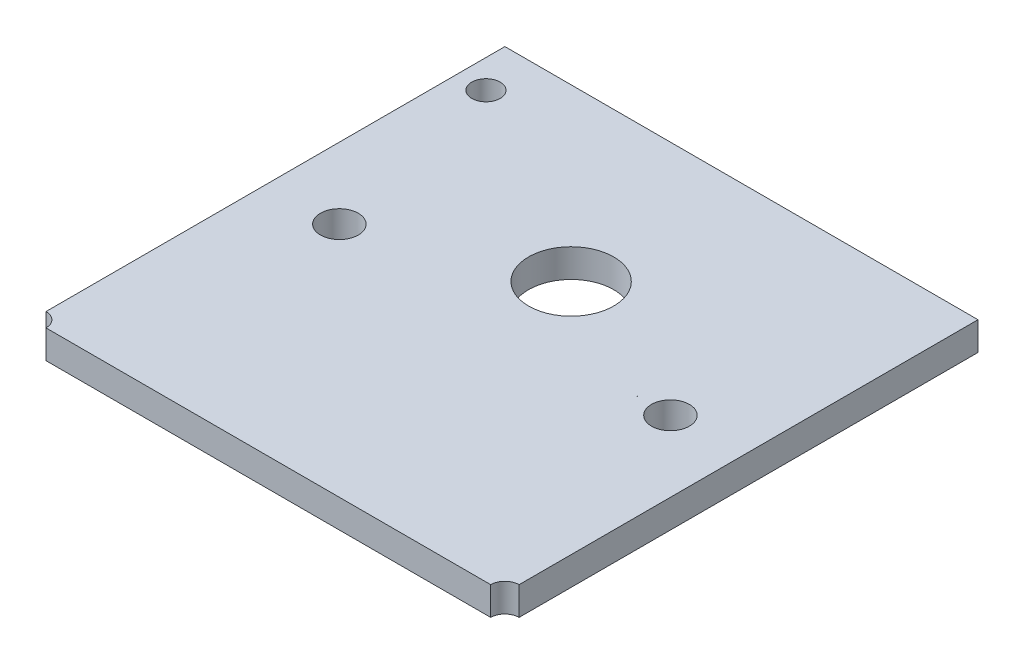
SolidWorks part; units mm, degrees
ref_plane "Front Plane" through (0, 0, 0) normal (0, 0, 1) x (1, 0, 0)
ref_plane "Top Plane" through (0, 0, 0) normal (0, 1, 0) x (1, 0, 0)
ref_plane "Right Plane" through (0, 0, 0) normal (1, 0, 0) x (0, 0, -1)
sketch "Sketch1" plane through (0, 0, 0) normal (0, 1, 0) x (1, 0, 0)
  line L0 (-25, 20) -> (25, 20) construction
  line L1 (-25, -25) -> (25, -25)
  line L2 (-25, -25) -> (-25, 25)
  line L3 (-25, 25) -> (25, 25)
  line L4 (25, -25) -> (25, 25)
  line L5 (-25, -25) -> (25, 25) construction
  line L6 (-25, 25) -> (25, -25) construction
  line L7 (-22, 25) -> (-22, -25) construction
  line L8 (-17.4954, -3.5) -> (-13.5554, -3.5)
  line L9 (-17.4954, 3.5) -> (-13.5554, 3.5)
  line L10 (0, 0) -> (0, -3.5) construction
  line L11 (17.4954, -3.5) -> (13.5554, -3.5)
  line L12 (17.4954, 3.5) -> (13.5554, 3.5)
  circle A0 centre (-22, 20) radius 1.5
  circle A1 centre (28, 20) radius 1.5
  circle A2 centre (25, -25) radius 1.5
  circle A3 centre (-25, -25) radius 1.5
  circle A8 centre (0, 0) radius 14
  circle A9 centre (0, 7) radius 4.5
  arc A10 (-17.4954, 3.5) -> (-17.4954, -3.5) centre (-17.4954, 0) ccw
  circle A11 centre (-17.4954, 0) radius 2
  circle A12 centre (17.4954, 0) radius 2
  arc A13 (17.4954, 3.5) -> (17.4954, -3.5) centre (17.4954, 0) cw
  arc A14 (-13.9991, -0.1597) -> (-13.9991, 0.1597) centre (-17.4954, 0) ccw
  arc A15 (13.9991, -0.1597) -> (13.9991, 0.1597) centre (17.4954, 0) cw
  point P0 (0, 0)
  dimension "D5" = 2
  dimension "D6" = 28
  dimension "D7" = 7
  dimension "D8" = 3.94
  dimension "D10" = 7
  dimension "D11" = 3
  dimension "D12" = 3
  dimension "D13" = 3
  dimension "D14" = 50
  dimension "D1" = 50
  dimension "D2" = 50
  dimension "D3" = 3
  dimension "D4" = 5
  dimension "D9" = 3.94
extrude "Boss-Extrude1" add sketch "Sketch1" along normal blind 3 contours L1 L4 L3 L2 A2 A1 A0 A3 L12 A13 L11 A8 L8 A10 L9 | A8 A15 A14 A9 | L9 A10 L8 A8 A11 | A13 L12 A8 L11 A12 region at (-23.4393, 0, 23.4393) region at (-20.8933, 0, 0) region at (0, 0, 0.8065) region at (13.9794, 0, 1.8567)
